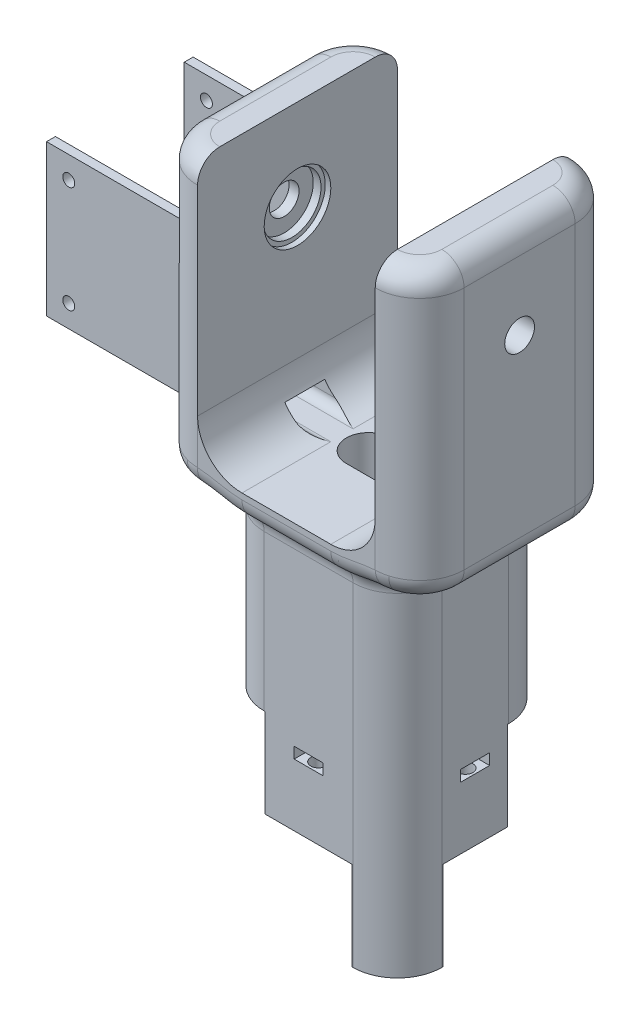
SolidWorks part; units mm, degrees
ref_plane "Plan de face" through (0, 0, 0) normal (0, 0, 1) x (1, 0, 0)
ref_plane "Plan de dessus" through (0, 0, 0) normal (0, 1, 0) x (1, 0, 0)
ref_plane "Plan de droite" through (0, 0, 0) normal (1, 0, 0) x (0, 0, -1)
sketch "Esquisse1" plane through (0, 0, 0) normal (0, 1, 0) x (1, 0, 0)
  line L1 (-20, -17.5) -> (20, -17.5)
  line L2 (-20, -17.5) -> (-20, 17.5)
  line L3 (-20, 17.5) -> (20, 17.5)
  line L4 (20, -17.5) -> (20, 17.5)
  line L5 (-20, -17.5) -> (20, 17.5) construction
  line L6 (-20, 17.5) -> (20, -17.5) construction
  point P0 (0, 0)
  dimension "D1" = 40
  dimension "D2" = 35
extrude "Boss.-Extru.1" add sketch "Esquisse1" along normal blind 80
fillet "Congé1" radius 10 4 edges at (-20, 40, 17.5) (-20, 40, -17.5) (20, 40, -17.5) (20, 40, 17.5)
sketch "Esquisse4" plane through (0, 0, 0) normal (0, -1, 0) x (1, 0, 0)
  line L10 (-20, 17.5) -> (9.8, 17.5)
  line L11 (9.8, 17.5) -> (9.8, 7.3)
  line L12 (9.8, 7.3) -> (20, 7.3)
  line L13 (20, 7.5) -> (20, -7.5) construction
  line L14 (20, 7.3) -> (20, -17.5)
  line L15 (20, -17.5) -> (-9.8, -17.5)
  line L16 (-9.8, -17.5) -> (-9.8, -7.3)
  line L17 (-9.8, -7.3) -> (-20, -7.3)
  line L18 (-20, -7.5) -> (-20, 7.5) construction
  line L19 (-20, -7.3) -> (-20, 17.5)
  line L20 (-10, 17.5) -> (10, 17.5) construction
  line L21 (10, -17.5) -> (-10, -17.5) construction
  arc A2 (-20, -7.5) -> (-10, -17.5) centre (-10, -7.5) ccw construction
  arc A3 (20, 7.5) -> (10, 17.5) centre (10, 7.5) ccw construction
  dimension "D1" = 0.2
  dimension "D2" = 0.2
  dimension "D3" = 0.2
  dimension "D4" = 0.2
extrude "Enlèv. mat.-Extru.3" cut sketch "Esquisse4" against normal blind 20
sketch "Esquisse5" plane through (0, 20, 0) normal (0, -1, 0) x (1, 0, 0)
  line L0 (-20, 7.5) -> (-20, -7.3) construction
  line L9 (-9.8, 7.3) -> (-20, 7.3)
  line L10 (-9.8, 7.3) -> (-9.8, 17.5)
  line L11 (-9.8, 17.5) -> (-20, 17.5)
  line L12 (-20, 7.3) -> (-20, 17.5)
  line L13 (20, -17.5) -> (9.8, -17.5)
  line L14 (20, -17.5) -> (20, -7.3)
  line L15 (20, -7.3) -> (9.8, -7.3)
  line L16 (9.8, -17.5) -> (9.8, -7.3)
  line L17 (9.8, 17.5) -> (-10, 17.5) construction
  line L18 (20, -7.5) -> (20, 7.3) construction
  line L19 (-9.8, -17.5) -> (10, -17.5) construction
  arc A0 (-10, 17.5) -> (-20, 7.5) centre (-10, 7.5) ccw construction
  arc A1 (10, -17.5) -> (20, -7.5) centre (10, -7.5) ccw construction
  dimension "D1" = 0.2
  dimension "D2" = 0.2
  dimension "D3" = 0.2
  dimension "D4" = 0.2
extrude "Enlèv. mat.-Extru.4" cut sketch "Esquisse5" against normal blind 20
sketch "Esquisse6" plane through (0, 80, 0) normal (0, 1, 0) x (1, 0, 0)
  line L1 (-30, -22.5) -> (30, -22.5)
  line L2 (-30, -22.5) -> (-30, 22.5)
  line L3 (-30, 22.5) -> (30, 22.5)
  line L4 (30, -22.5) -> (30, 22.5)
  line L5 (-30, -22.5) -> (30, 22.5) construction
  line L6 (-30, 22.5) -> (30, -22.5) construction
  point P0 (0, 0)
  dimension "D1" = 45
  dimension "D2" = 60
extrude "Boss.-Extru.2" add sketch "Esquisse6" along normal blind 65
fillet "Congé2" radius 10 4 edges at (-30, 112.5, -22.5) (-30, 112.5, 22.5) (30, 112.5, -22.5) (30, 112.5, 22.5)
fillet "Congé5" radius 5 8 edges at (-17.0711, 80, -14.5711) (-17.0711, 80, 14.5711) (-20, 80, 0) (0, 80, -17.5) (17.0711, 80, -14.5711) (20, 80, 0) (17.0711, 80, 14.5711) (0, 80, 17.5)
fillet "Congé7" radius 5 8 edges at (27.0711, 145, -19.5711) (30, 145, 0) (27.0711, 145, 19.5711) (0, 145, 22.5) (-27.0711, 145, 19.5711) (-30, 145, 0) (-27.0711, 145, -19.5711) (0, 145, -22.5)
sketch "Esquisse7" plane through (0, 0, 17.5) normal (0, 0, 1) x (1, 0, 0)
  line L0 (-20, 145) -> (20, 145) construction
  line L1 (-20, 145) -> (20, 145)
  line L2 (-20, 145) -> (-20, 85)
  line L3 (-20, 85) -> (20, 85)
  line L4 (20, 145) -> (20, 85)
  line L5 (30, 140) -> (30, 80) construction
  dimension "D1" = 60
  dimension "D2" = 40
  dimension "D3" = 10
extrude "Enlèv. mat.-Extru.5" cut sketch "Esquisse7" against normal through all and the other way through all
fillet "Congé8" radius 10 2 edges at (20, 85, 0) (-20, 85, 0)
sketch "Esquisse8" plane through (-30, 0, 0) normal (-1, 0, 0) x (0, 0, 1)
  line L0 (-22.5, 140) -> (2.5, 140) construction
  line L1 (-14.5, 138) -> (14.5, 138)
  line L2 (-14.5, 138) -> (-14.5, 89.5)
  line L3 (-14.5, 89.5) -> (14.5, 89.5)
  line L4 (14.5, 138) -> (14.5, 89.5)
  line L5 (-22.5, 140) -> (-22.5, 95) construction
  dimension "D1" = 29
  dimension "D2" = 48.5
  dimension "D3" = 2
  dimension "D4" = 8
extrude "Enlèv. mat.-Extru.6" cut sketch "Esquisse8" against normal blind 4.75
sketch "Esquisse9" plane through (-30, 0, 0) normal (-1, 0, 0) x (0, 0, 1)
  line L0 (-14.5, 138) -> (-14.5, 89.5) construction
  line L1 (-16.5, 125.5) -> (-14.5, 125.5)
  line L2 (-16.5, 125.5) -> (-16.5, 91.5)
  line L3 (-16.5, 91.5) -> (-14.5, 91.5)
  line L4 (-14.5, 125.5) -> (-14.5, 91.5)
  line L5 (16.5, 125.5) -> (14.5, 125.5)
  line L6 (16.5, 125.5) -> (16.5, 91.5)
  line L7 (16.5, 91.5) -> (14.5, 91.5)
  line L8 (14.5, 125.5) -> (14.5, 91.5)
  line L9 (14.5, 89.5) -> (14.5, 138) construction
  line L10 (-12.5, 89.5) -> (12.5, 89.5) construction
  dimension "D1" = 34
  dimension "D2" = 34
  dimension "D3" = 2
  dimension "D4" = 2
  dimension "D5" = 2
  dimension "D6" = 2
extrude "Boss.-Extru.3" add sketch "Esquisse9" along normal blind 30 and the other way blind 5
sketch "Esquisse10" plane through (-25.25, 0, 0) normal (-1, 0, 0) x (0, 0, 1)
  line L0 (-14.5, 89.5) -> (14.5, 89.5) construction
  line L1 (14.5, 89.5) -> (14.5, 138) construction
  circle A0 centre (0, 124.5) radius 3.35
  dimension "D1" = 6.7
  dimension "D2" = 35
  dimension "D3" = 14.5
extrude "Enlèv. mat.-Extru.7" cut sketch "Esquisse10" against normal through all
sketch "Esquisse11" plane through (0, 0, 16.5) normal (0, 0, 1) x (1, 0, 0)
  line L0 (-29.1652, 125.5) -> (-60, 125.5) construction
  line L1 (-60, 91.5) -> (-60, 125.5) construction
  circle A0 centre (-55, 120.5) radius 1.35
  circle A1 centre (-55, 96.5) radius 1.35
  dimension "D1" = 2.7
  dimension "D2" = 2.7
  dimension "D3" = 24
  dimension "D4" = 5
  dimension "D5" = 5
extrude "Enlèv. mat.-Extru.8" cut sketch "Esquisse11" against normal through all
sketch "Esquisse12" plane through (-20, 0, 0) normal (1, 0, 0) x (0, 0, -1)
  circle A0 centre (0, 124.5) radius 6.55
  dimension "D1" = 13.1
extrude "Enlèv. mat.-Extru.9" cut sketch "Esquisse12" against normal blind 3
sketch "Esquisse13" plane through (-20, 0, 0) normal (1, 0, 0) x (0, 0, -1)
  circle A0 centre (0, 124.5) radius 7.5
  dimension "D1" = 15
extrude "Enlèv. mat.-Extru.10" cut sketch "Esquisse13" against normal blind 1.25
sketch "Esquisse14" plane through (20, 0, 0) normal (-1, 0, 0) x (0, 0, 1)
  circle A0 centre (0, 124.5) radius 6.55
  dimension "D1" = 13.1
extrude "Enlèv. mat.-Extru.11" cut sketch "Esquisse14" against normal blind 4
sketch "Esquisse15" plane through (20, 0, 0) normal (-1, 0, 0) x (0, 0, 1)
  circle A0 centre (0, 124.5) radius 7.5
  dimension "D1" = 15
extrude "Enlèv. mat.-Extru.12" cut sketch "Esquisse15" against normal blind 1.25
sketch "Esquisse16" plane through (0, 85, 0) normal (0, 1, 0) x (1, 0, 0)
  line L0 (-4, 0) -> (4, 0) construction
  line L1 (-4, 5) -> (4, 5)
  line L2 (-4, -5) -> (4, -5)
  arc A0 (-4, 5) -> (-4, -5) centre (-4, 0) ccw
  arc A1 (4, -5) -> (4, 5) centre (4, 0) ccw
  point P2 (0, 0)
  dimension "D2" = 5
  dimension "D1" = 8
extrude "Enlèv. mat.-Extru.13" cut sketch "Esquisse16" against normal through all and the other way through all
sketch "Esquisse17" plane through (-30, 0, 0) normal (-1, 0, 0) x (0, 0, 1)
  line L0 (-2.5, 87) -> (2.5, 87) construction
  line L1 (-2.5, 89) -> (2.5, 89)
  line L2 (-2.5, 85) -> (2.5, 85)
  line L5 (22.5, 95) -> (22.5, 80) construction
  line L6 (-14.5, 89.5) -> (14.5, 89.5) construction
  arc A0 (-2.5, 89) -> (-2.5, 85) centre (-2.5, 87) ccw
  arc A1 (2.5, 85) -> (2.5, 89) centre (2.5, 87) ccw
  point P2 (0, 87)
  dimension "D2" = 2
  dimension "D1" = 5
  dimension "D3" = 22.5
  dimension "D4" = 0.5
extrude "Enlèv. mat.-Extru.14" cut sketch "Esquisse17" against normal blind 20
fillet "Congé9" radius 5 12 edges at (0, 80, -22.5) (-27.0711, 80, -19.5711) (-30, 80, 0) (-27.0711, 80, 19.5711) (-15, 80, 22.5) (-15, 80, -22.5) (15, 80, 22.5) (27.0711, 80, 19.5711) (30, 80, 0) (27.0711, 80, -19.5711) (15, 80, -22.5) (0, 80, 22.5)
sketch "Esquisse18" plane through (-30, 0, 0) normal (-1, 0, 0) x (0, 0, 1)
  line L0 (-4.5, 87) -> (-4.5, 89.5)
  line L1 (-14.5, 89.5) -> (14.5, 89.5) construction
  line L2 (-4.5, 89.5) -> (4.5, 89.5)
  line L3 (4.5, 89.5) -> (4.5, 87)
  line L4 (4.5, 87) -> (-4.5, 87)
  arc A0 (-2.5, 89) -> (-2.5, 85) centre (-2.5, 87) ccw construction
  arc A1 (2.5, 85) -> (2.5, 89) centre (2.5, 87) ccw construction
extrude "Enlèv. mat.-Extru.15" cut sketch "Esquisse18" against normal blind 20
sketch "Esquisse19" plane through (0, 20, 0) normal (0, -1, 0) x (-1, 0, 0)
  line L0 (9.8, 17.5) -> (-9.8, 17.5) construction
  circle A0 centre (0, 15.3) radius 1.7
  dimension "D1" = 3.4
  dimension "D2" = 2.2
extrude "Enlèv. mat.-Extru.16" cut sketch "Esquisse19" against normal blind 20
sketch "Esquisse20" plane through (0, 0, -17.5) normal (0, 0, -1) x (-1, 0, 0)
  line L0 (9.8, 20) -> (-9.8, 20) construction
  line L1 (-3.25, 36.5) -> (3.25, 36.5)
  line L2 (-3.25, 36.5) -> (-3.25, 34)
  line L3 (-3.25, 34) -> (3.25, 34)
  line L4 (3.25, 36.5) -> (3.25, 34)
  line L5 (-3.25, 36.5) -> (3.25, 34) construction
  line L6 (-3.25, 34) -> (3.25, 36.5) construction
  point P0 (0, 35.25)
  dimension "D1" = 14
  dimension "D2" = 6.5
  dimension "D3" = 2.5
extrude "Enlèv. mat.-Extru.17" cut sketch "Esquisse20" against normal blind 5.8
sketch "Esquisse21" plane through (0, 20, 0) normal (0, -1, 0) x (1, 0, 0)
  line L0 (-20, 7.3) -> (-20, -7.3) construction
  circle A0 centre (-17.8, 0) radius 1.7
  dimension "D1" = 3.4
  dimension "D2" = 2.2
extrude "Enlèv. mat.-Extru.18" cut sketch "Esquisse21" against normal blind 20
sketch "Esquisse22" plane through (-20, 0, 0) normal (-1, 0, 0) x (0, 0, 1)
  line L0 (7.3, 20) -> (-7.3, 20) construction
  line L1 (-3.25, 36.5) -> (3.25, 36.5)
  line L2 (-3.25, 36.5) -> (-3.25, 34)
  line L3 (-3.25, 34) -> (3.25, 34)
  line L4 (3.25, 36.5) -> (3.25, 34)
  line L5 (-3.25, 36.5) -> (3.25, 34) construction
  line L6 (-3.25, 34) -> (3.25, 36.5) construction
  point P0 (0, 35.25)
  dimension "D1" = 6.5
  dimension "D2" = 2.5
  dimension "D3" = 14
extrude "Enlèv. mat.-Extru.19" cut sketch "Esquisse22" against normal blind 5.8
mirror "Symétrie1" about plane through (0, 0, 0) normal (0, 0, 1) of "Enlèv. mat.-Extru.17", "Enlèv. mat.-Extru.16"
mirror "Symétrie2" about plane through (0, 0, 0) normal (1, 0, 0) of "Enlèv. mat.-Extru.19", "Enlèv. mat.-Extru.18"
equation "\"1.25.00mm\"=4"
